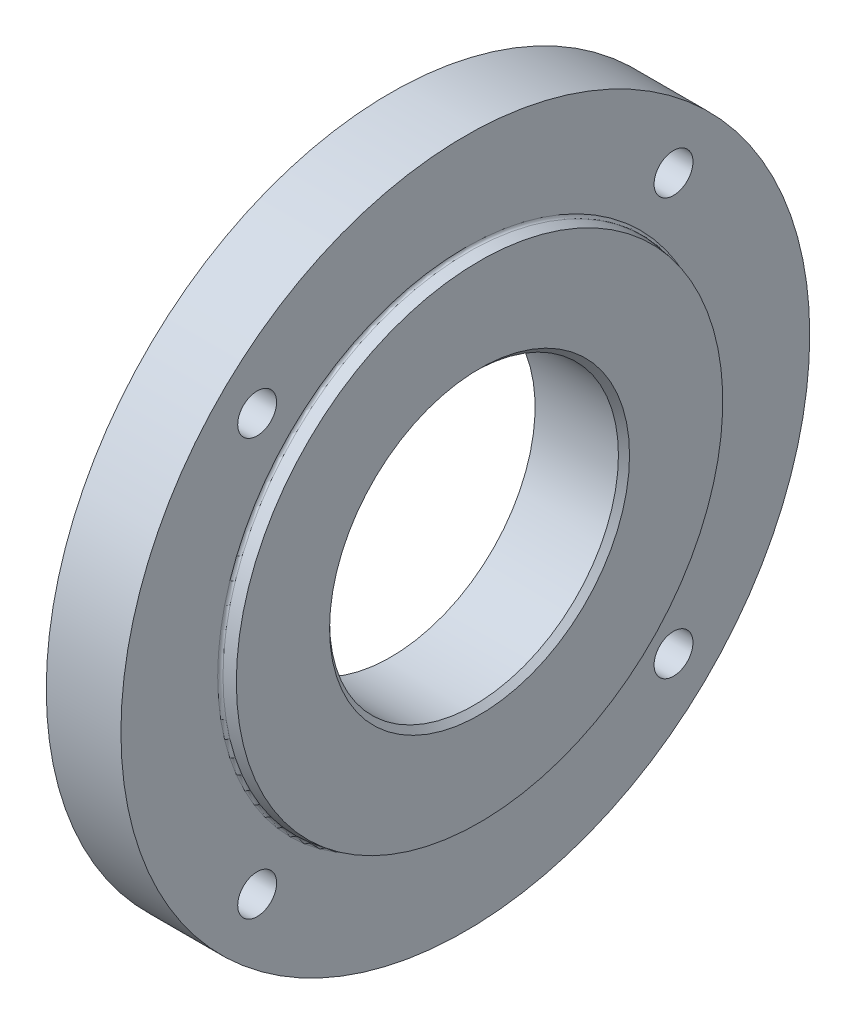
SolidWorks part; units mm, degrees
ref_plane "Front Plane" through (0, 0, 0) normal (0, 0, 1) x (1, 0, 0)
ref_plane "Top Plane" through (0, 0, 0) normal (0, 1, 0) x (1, 0, 0)
ref_plane "Right Plane" through (0, 0, 0) normal (1, 0, 0) x (0, 0, -1)
sketch "Sketch1" plane through (0, 0, 0) normal (0, 0, 1) x (1, 0, 0)
  line L0 (0, 0) -> (131.8697, 0) construction
  line L1 (0, 41.275) -> (0, 98.425)
  line L2 (0, 98.425) -> (21.336, 98.425)
  line L3 (21.336, 98.425) -> (21.336, 70.0151)
  line L4 (21.336, 70.0151) -> (25.4, 70.0151)
  line L5 (25.4, 70.0151) -> (25.4, 41.275)
  line L6 (25.4, 41.275) -> (0, 41.275)
  dimension "D1" = 25.4
  dimension "D2" = 4.064
  dimension "D3" = 41.275
  dimension "D4" = 70.0151
  dimension "D5" = 98.425
revolve "Revolve1" add sketch "Sketch1" angle 360 about L0
sketch "Sketch2" plane through (21.336, 0, 0) normal (1, 0, 0) x (0, 0, -1)
  line L0 (0, 0) -> (84.1375, 0) construction
  line L1 (0, 0) -> (59.4942, 59.4942) construction
  circle A0 centre (0, 0) radius 84.1375 construction
  circle A1 centre (59.4942, 59.4942) radius 5.5563
  dimension "D1" = 168.275
  dimension "D3" = 11.1125
  dimension "D2" = 45
extrude "Cut-Extrude1" cut sketch "Sketch2" against normal through all
pattern_circular "CirPattern1" count 4 over 360 about axis through (0, 0, 0) along (-1, 0, 0) of "Cut-Extrude1" reverse direction yes
chamfer "Chamfer1" distance 0.508 distance2 3.302 1 edges at (25.4, 0, 70.0151) first distance on face at (25.4, 0, 70.0151)
chamfer "Chamfer2" distance 1.5875 angle 45 1 edges at (25.4, 0, 41.275)
fillet "Fillet1" radius 0.762 1 edges at (21.336, 0, 70.0151)
